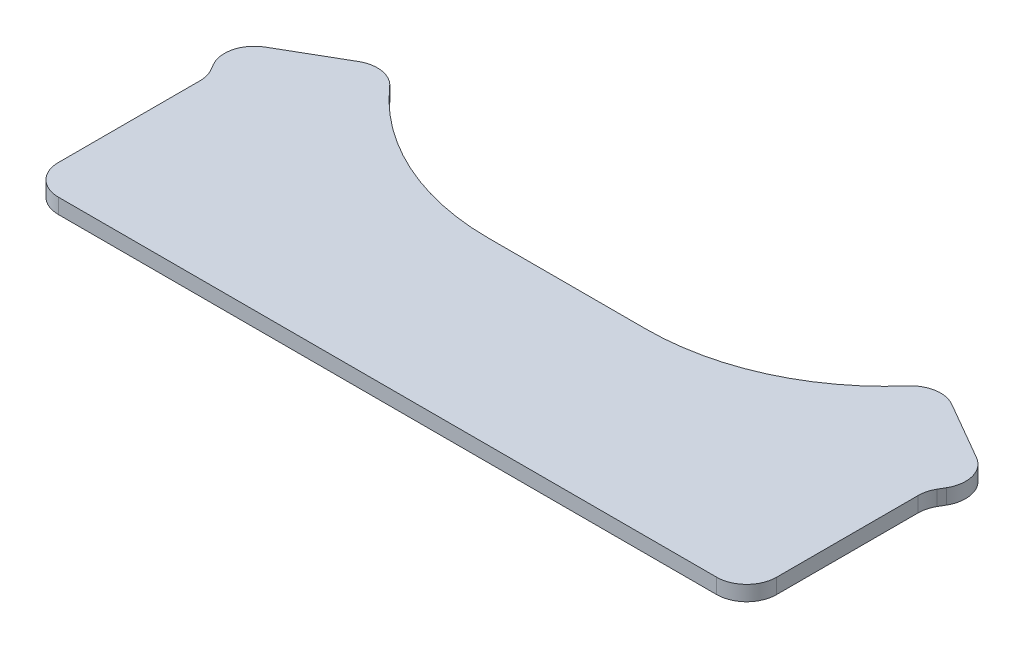
SolidWorks part; units mm, degrees
material "FR4_stuffedProtoboard"
ref_plane "Front Plane" through (0, 0, 0) normal (0, 0, 1) x (1, 0, 0)
ref_plane "Top Plane" through (0, 0, 0) normal (0, 1, 0) x (1, 0, 0)
ref_plane "Right Plane" through (0, 0, 0) normal (1, 0, 0) x (0, 0, -1)
sketch "Sketch1" plane through (0, 0, 0) normal (0, 1, 0) x (1, 0, 0)
  line L0 (-38.1, 9.525) -> (38.1, -9.525) construction
  line L1 (-38.1, 9.525) -> (38.1, 9.525)
  line L2 (-38.1, 9.525) -> (-38.1, -9.525)
  line L3 (-38.1, -9.525) -> (38.1, -9.525)
  line L4 (38.1, 9.525) -> (38.1, -9.525)
  point P4 (0, 0)
  dimension "D1" = 19.05
  dimension "D2" = 76.2
extrude "Boss-Extrude1" add sketch "Sketch1" along normal blind 1.6
sketch "Sketch2" plane through (0, 0, 0) normal (0, -1, 0) x (1, 0, 0)
  line L0 (0, 43.3118) -> (-53.8944, -50.0361) construction
  line L1 (0, -0.88) -> (0, 0.88) construction
  line L2 (-38.1, 9.525) -> (38.1, 9.525) construction
  line L3 (-40.4812, -13.6494) -> (-29.0892, -20.2266)
  line L4 (-29.0892, -20.2266) -> (-22.9106, -9.525)
  line L5 (-22.9106, -9.525) -> (-34.3027, -2.9478)
  line L6 (-34.3027, -2.9478) -> (-40.4812, -13.6494)
  line L7 (38.1, -9.525) -> (-38.1, -9.525) construction
  point P2 (-34.7852, -16.938)
  point P5 (-49.537, -6.5559)
  point P6 (-23.3449, -7.1863)
  point P9 (-31.269, -22.5887)
  point P12 (0, 0)
  dimension "D1" = 33.7868
  dimension "D2" = 30
  dimension "D3" = 4.7625
fillet "Fillet1" [suppressed] radius 3.175
extrude "Boss-Extrude2" add sketch "Sketch2" against normal up to surface (1.6 mm away) up to face at (0, 1.6, 0)
mirror "Mirror1" about plane through (0, 0, 0) normal (1, 0, 0) of "Boss-Extrude2"
fillet "Fillet2" radius 25.4 2 edges at (22.9106, 0.8, -9.525) (-22.9106, 0.8, -9.525)
fillet "Fillet3" radius 3.175 8 edges at (38.1, 0.8, 9.525) (-38.1, 0.8, 9.525) (-38.1, 0.8, -9.525) (-40.4812, 0.8, -13.6494) (-29.0892, 0.8, -20.2266) (40.4812, 0.8, -13.6494) (38.1, 0.8, -9.525) (29.0892, 0.8, -20.2266)
